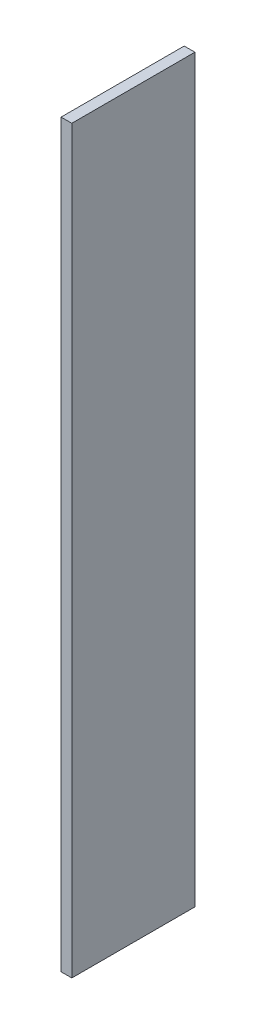
SolidWorks part; units mm, degrees
material "6061-T6 (SS)"
ref_plane "Front" through (0, 0, 0) normal (0, 0, 1) x (1, 0, 0)
ref_plane "Top" through (0, 0, 0) normal (0, 1, 0) x (1, 0, 0)
ref_plane "Right" through (0, 0, 0) normal (1, 0, 0) x (0, 0, -1)
sketch "Sketch1" plane through (0, 0, 0) normal (0, 1, 0) x (1, 0, 0)
  line L1 (-50.8, 584.2) -> (50.8, 584.2)
  line L2 (-50.8, 584.2) -> (-50.8, -584.2)
  line L3 (-50.8, -584.2) -> (50.8, -584.2)
  line L4 (50.8, 584.2) -> (50.8, -584.2)
  line L5 (-50.8, 584.2) -> (50.8, -584.2) construction
  line L6 (-50.8, -584.2) -> (50.8, 584.2) construction
  point P0 (0, 0)
  dimension "D1" = 1168.4
  dimension "D2" = 101.6
extrude "Boss-Extrude1" add sketch "Sketch1" along normal blind 7023.1
sketch "Sketch2" plane through (50.8, 0, 0) normal (1, 0, 0) x (0, 0, -1)
  line L0 (584.2, 7023.1) -> (584.2, 0) construction
  line L1 (584.2, 0) -> (431.8, 0)
  line L2 (584.2, 0) -> (584.2, 2286)
  line L3 (584.2, 2286) -> (431.8, 2286)
  line L4 (431.8, 0) -> (431.8, 2286)
  line L6 (-584.2, 0) -> (584.2, 0) construction
  dimension "D1" = 152.4
  dimension "D2" = 2286
extrude "Cut-Extrude1" [suppressed] cut sketch "Sketch2" against normal through all
sketch "Sketch3" [suppressed] plane through (50.8, 0, 0) normal (1, 0, 0) x (0, 0, -1)
  line L2 (-381, 1944.6548) -> (-381, 0)
  line L4 (381, 0) -> (815.975, 0) construction
  line L5 (381, 0) -> (-381, 0)
  line L6 (584.2, 7124.7) -> (584.2, 0) construction
  line L12 (381, 1944.6548) -> (381, 0)
  line L13 (-381, 1944.6548) -> (381, 1944.6548)
  dimension "D2" = 1944.6548
  dimension "D1" = 762
  dimension "D3" = 203.2
extrude "Cut-Extrude2" [suppressed] cut sketch "Sketch3" against normal through all
sketch "Sketch4" [suppressed] plane through (-76.2, 0, 0) normal (-1, 0, 0) x (0, 0, 1)
  line L0 (-584.2, 6400.8) -> (584.2, 6400.8) construction
  line L1 (584.2, 6400.8) -> (584.2, 0) construction
  circle A0 centre (177.8, 5994.4) radius 152.4
  dimension "D1" = 304.8
  dimension "D2" = 406.4
  dimension "D3" = 406.4
extrude "Cut-Extrude3" [suppressed] cut sketch "Sketch4" against normal through all and the other way through all
sketch "Sketch5" [suppressed] plane through (-76.2, 0, 0) normal (-1, 0, 0) x (0, 0, 1)
  line L0 (584.2, 6400.8) -> (584.2, 0) construction
  line L1 (-584.2, 0) -> (584.2, 0) construction
  circle A0 centre (177.8, 406.4) radius 152.4
  dimension "D1" = 304.8
  dimension "D2" = 406.4
  dimension "D3" = 406.4
extrude "Cut-Extrude4" [suppressed] cut sketch "Sketch5" against normal through all
sketch "Sketch6" [suppressed] plane through (50.8, 0, 0) normal (1, 0, 0) x (0, 0, -1)
  line L0 (-584.2, 7023.1) -> (-584.2, 0) construction
  line L1 (584.2, 0) -> (-584.2, 0)
  line L2 (584.2, 0) -> (584.2, 4267.2)
  line L3 (584.2, 4267.2) -> (-584.2, 4267.2)
  line L4 (-584.2, 0) -> (-584.2, 4267.2)
  dimension "D1" = 4267.2
extrude "Cut-Extrude5" [suppressed] cut sketch "Sketch6" against normal through all
sketch "Sketch7" [suppressed] plane through (50.8, 0, 0) normal (1, 0, 0) x (0, 0, -1)
  line L1 (-584.2, 0) -> (215.9, 0)
  line L2 (-584.2, 0) -> (-584.2, 4267.2)
  line L3 (-584.2, 4267.2) -> (215.9, 4267.2)
  line L4 (215.9, 0) -> (215.9, 4267.2)
  dimension "D1" = 4267.2
  dimension "D2" = 800.1
extrude "Cut-Extrude6" [suppressed] cut sketch "Sketch7" against normal through all
sketch "Sketch8" [suppressed] plane through (0, 1944.6548, 0) normal (0, -1, 0) x (1, 0, 0)
  line L0 (50.8, 381) -> (431.8, -278.9114)
  line L1 (431.8, -278.9114) -> (354.8103, -323.3614)
  line L2 (354.8103, -323.3614) -> (-26.1897, 336.55)
  line L3 (-26.1897, 336.55) -> (50.8, 381)
  line L4 (50.8, -381) -> (50.8, 381) construction
  dimension "D1" = 762
  dimension "D2" = 88.9
  dimension "D3" = 70
extrude "Boss-Extrude2" [suppressed] add sketch "Sketch8" along normal up to surface (1944.6548 mm away) separate body up to face at (0, 0, 0)
